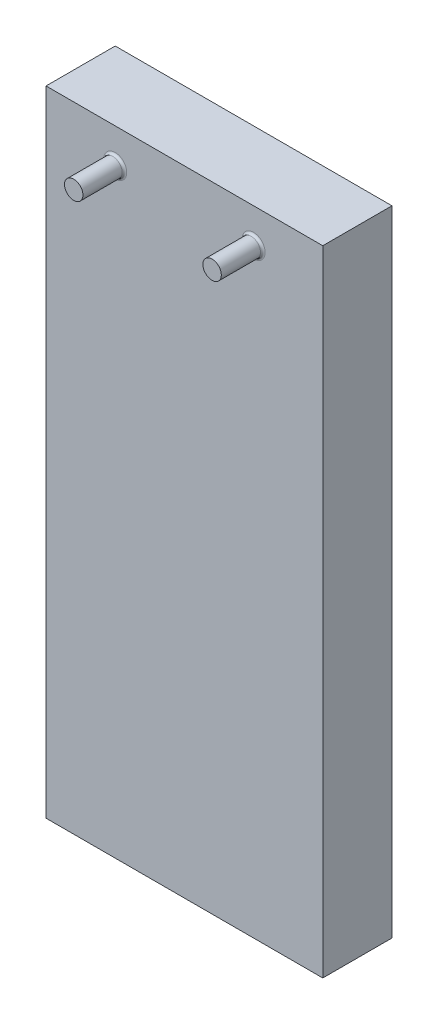
SolidWorks part; units mm, degrees
ref_plane "Front Plane" through (0, 0, 0) normal (0, 0, 1) x (1, 0, 0)
ref_plane "Top Plane" through (0, 0, 0) normal (0, 1, 0) x (1, 0, 0)
ref_plane "Right Plane" through (0, 0, 0) normal (1, 0, 0) x (0, 0, -1)
sketch "Sketch1" plane through (0, 0, 0) normal (0, 1, 0) x (1, 0, 0)
  line L1 (-60, -15) -> (60, -15)
  line L2 (-60, -15) -> (-60, 15)
  line L3 (-60, 15) -> (60, 15)
  line L4 (60, -15) -> (60, 15)
  line L5 (-60, -15) -> (60, 15) construction
  line L6 (-60, 15) -> (60, -15) construction
  point P0 (0, 0)
  dimension "D1" = 120
  dimension "D2" = 30
extrude "Boss-Extrude1" add sketch "Sketch1" along normal blind 275
sketch "Sketch2" plane through (0, 0, 15) normal (0, 0, 1) x (1, 0, 0)
  line L0 (-60, 245) -> (60, 245)
  line L1 (-60, 275) -> (-60, 0) construction
  line L2 (60, 275) -> (60, 0) construction
  line L3 (-60, 275) -> (60, 275) construction
  line L4 (-60, 245) -> (-60, 275)
  line L5 (-60, 260) -> (60, 260) construction
  circle A2 centre (-30, 260) radius 4
  circle A3 centre (30, 260) radius 4
  dimension "D4" = 8
  dimension "D1" = 30
  dimension "D2" = 30
  dimension "D3" = 30
extrude "Boss-Extrude2" add sketch "Sketch2" along normal blind 18 contours L5 A3 | A3 L5 | L5 A2 | A2 L5 region at (-30, 261.6977, 15) region at (30, 261.6977, 15) region at (30, 258.3023, 15) region at (-30, 258.3023, 15)
fillet "Fillet1" radius 1 2 edges at (26, 260, 15) (-34, 260, 15)
equation "\"PCWidth\"= 242mm'Distance of longest part parallel to GPU(ussually GPU)"
equation "\"PCLength\"= 320mm'Length across I/O from PS to GPU"
equation "\"PCHeight\"= 172mm'Tallest point with mobo laying flat"
equation "\"WallThickness\"= 9mm'Thickness of each outer tank wall"
equation "\"ThermoBarrierThickness\"= 3mm'Thickness of barrier between hot side and cold side"
equation "\"HotSideGap\"= 35mm'Space in the hot side for a pump"
equation "\"PCClearance\"= 30mm'Clearance from top of tank to top of PC"
equation "\"RadiatorHeight\"= 275mm'Final Height from ground of radiators"
equation "\"D1@Boss-Extrude1\"=\"RadiatorHeight\""
